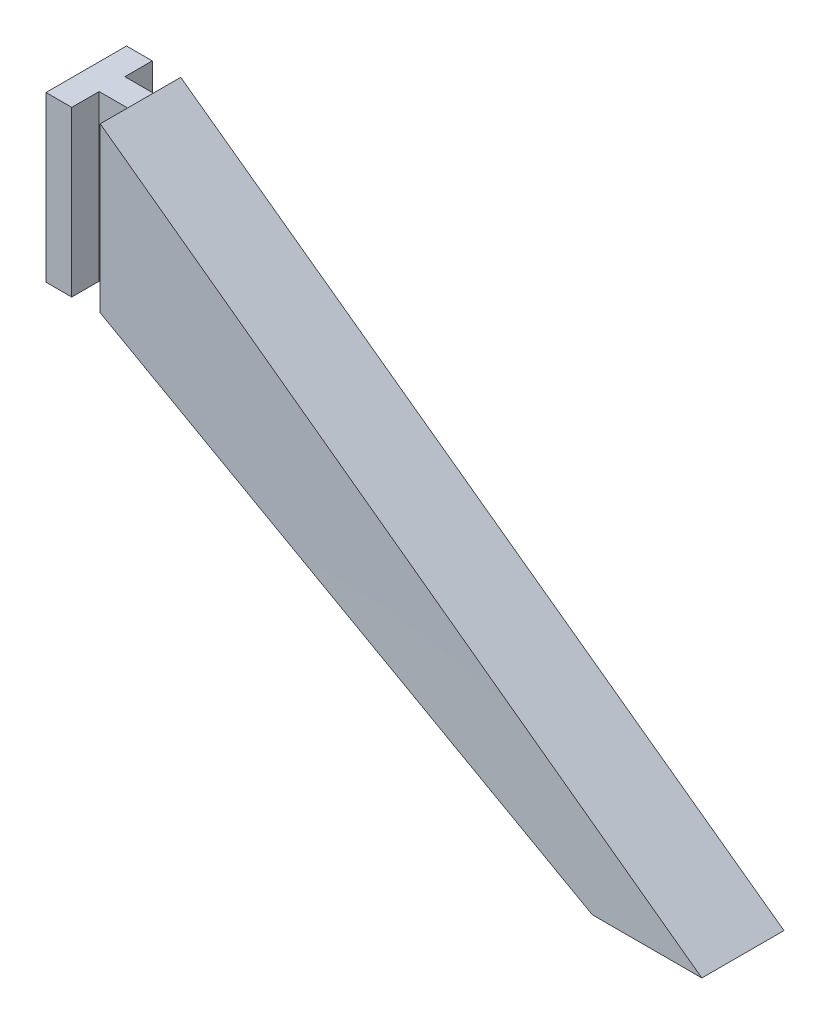
SolidWorks part; units mm, degrees
ref_plane "Front Plane" through (0, 0, 0) normal (0, 0, 1) x (1, 0, 0)
ref_plane "Top Plane" through (0, 0, 0) normal (0, 1, 0) x (1, 0, 0)
ref_plane "Right Plane" through (0, 0, 0) normal (1, 0, 0) x (0, 0, -1)
sketch "Sketch2" plane through (0, 0, 0) normal (0, 1, 0) x (1, 0, 0)
  line L0 (-9.9, 7.35) -> (-9.9, -7.35)
  line L1 (-9.9, -7.35) -> (-5.2, -7.35)
  line L2 (-5.2, -7.35) -> (-5.2, -2.35)
  line L3 (-5.2, -2.35) -> (0, -2.35)
  line L4 (0, -2.35) -> (0, 2.35)
  line L5 (0, 2.35) -> (-5.2, 2.35)
  line L6 (-5.2, 2.35) -> (-5.2, 7.35)
  line L7 (-5.2, 7.35) -> (-9.9, 7.35)
  point P2 (0, 0)
  dimension "D1" = 4.7
  dimension "D2" = 5.2
  dimension "D3" = 4.7
  dimension "D4" = 14.7
extrude "Boss-Extrude1" add sketch "Sketch2" along normal blind 30
sketch "Sketch3" plane through (0, 0, 0) normal (0, 0, 1) x (1, 0, 0)
  line L0 (0, 0) -> (100, 0)
  line L3 (100, 0) -> (100, 30)
  line L4 (100, 30) -> (0, 30)
  line L6 (0, 30) -> (0, 0)
  dimension "D4" = 100
extrude "Boss-Extrude2" [suppressed] add sketch "Sketch3" along normal blind 5 and the other way blind 5
sketch "Sketch4" [suppressed] plane through (0, 0, 0) normal (0, -1, 0) x (1, 0, 0)
  line L0 (0, 5) -> (100, 5) construction
  line L1 (100, -5) -> (90, -5)
  line L2 (100, -5) -> (100, 5)
  line L3 (100, 5) -> (90, 5)
  line L4 (90, -5) -> (90, 5)
extrude "Boss-Extrude3" [suppressed] add sketch "Sketch4" along normal blind 20 draft 7
ref_plane "Plane1" through (0, -50, 0) normal (0, 1, 0) x (1, 0, 0)
sketch "Sketch5" plane through (0, -50, 0) normal (0, 1, 0) x (1, 0, 0)
  line L6 (90, -7.5) -> (110, -7.5)
  line L7 (90, -7.5) -> (90, 7.5)
  line L8 (90, 7.5) -> (110, 7.5)
  line L9 (110, -7.5) -> (110, 7.5)
  line L10 (90, -7.5) -> (110, 7.5) construction
  line L11 (90, 7.5) -> (110, -7.5) construction
  point P1 (100, 0)
  point P6 (100, 7.5)
  point P8 (0, 0)
  dimension "D1" = 100
  dimension "D3" = 20
  dimension "D2" = 15
sketch "Sketch6" plane through (0, 0, 0) normal (1, 0, 0) x (0, 0, -1)
  line L0 (-7.35, 30) -> (7.35, 30)
  line L5 (-7.35, 30) -> (-7.35, 0.1043)
  line L6 (7.35, 30) -> (7.35, 0.1043)
  line L7 (-7.35, 0.1043) -> (7.35, 0.1043)
loft "Loft3" add profiles "Sketch6", "Sketch5" connector at (0, 30, 7.35) connector at (110, -50, 7.5)
